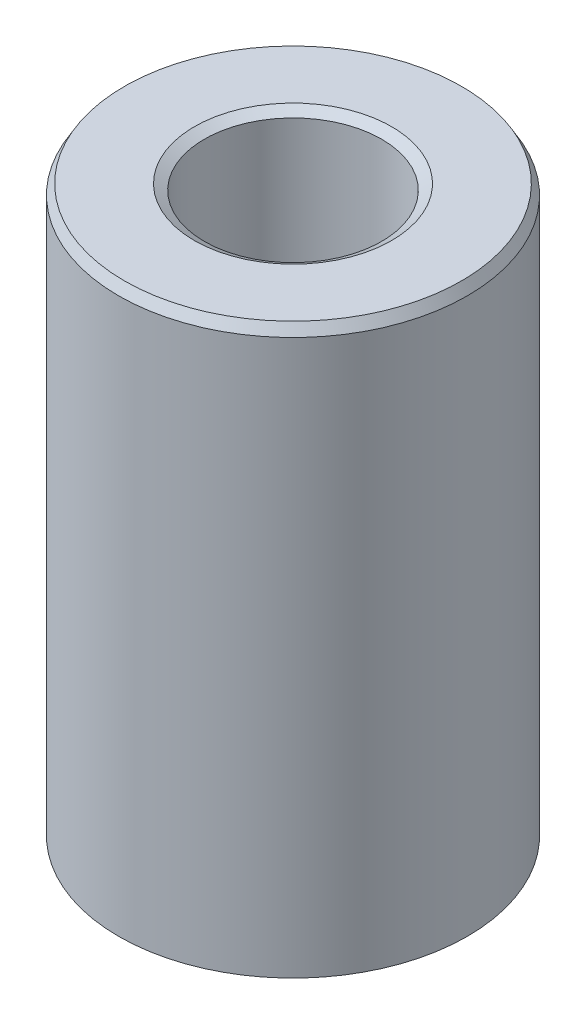
SolidWorks part; units mm, degrees
ref_plane "Front Plane" through (0, 0, 0) normal (0, 0, 1) x (1, 0, 0)
ref_plane "Top Plane" through (0, 0, 0) normal (0, 1, 0) x (1, 0, 0)
ref_plane "Right Plane" through (0, 0, 0) normal (1, 0, 0) x (0, 0, -1)
sketch "Sketch1" plane through (0, 0, 0) normal (0, 1, 0) x (1, 0, 0)
  circle A0 centre (0, 0) radius 42.5
  dimension "SLEEVE_OD" = 85
extrude "Boss-Extrude1" add sketch "Sketch1" along normal blind 139.097
sketch "Sketch2" plane through (0, 0, 0) normal (0, 1, 0) x (1, 0, 0)
  circle A0 centre (0, 0) radius 21.6071
  dimension "BORE_D" = 43.2143
extrude "Cut-Extrude1" cut sketch "Sketch2" along normal through all
chamfer "Chamfer1" distance 2.4461 angle 30 4 edges at (0, 139.097, 21.6071) (0, 0, 21.6071) (0, 0, 42.5) (0, 139.097, 42.5) first distance on face at (0, 139.097, 21.6071) first distance on face at (0, 0, 21.6071) first distance on face at (0, 139.097, 42.5)
